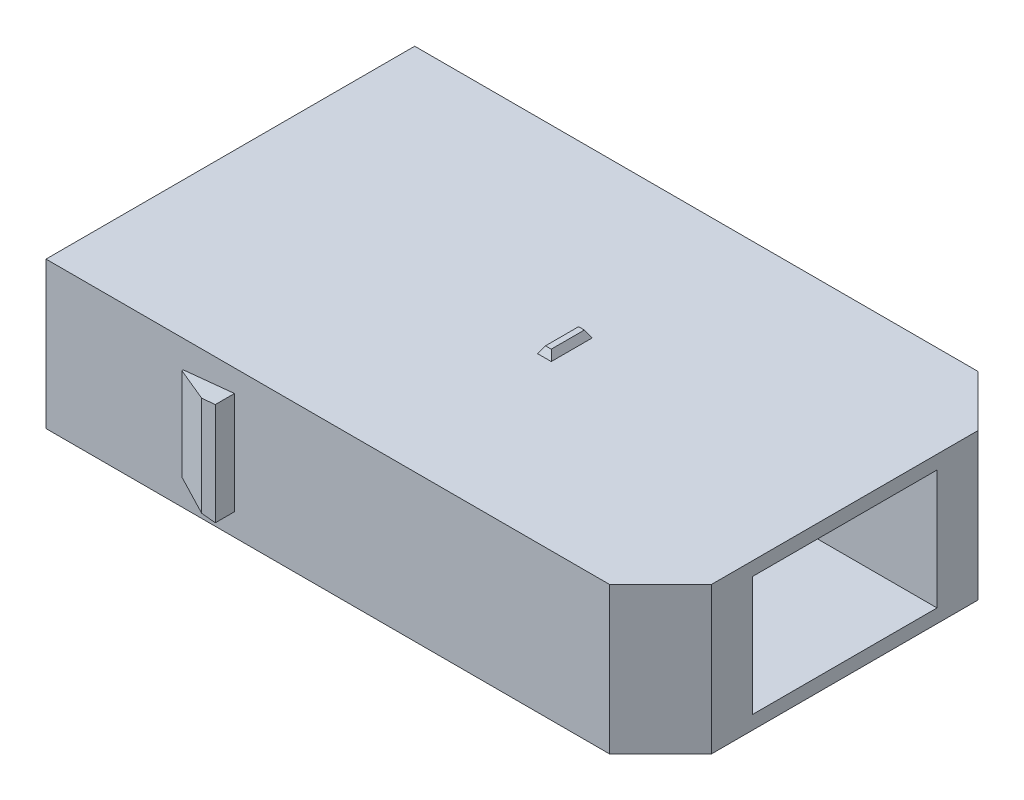
SolidWorks part; units mm, degrees
material "Perspex (TM) GS Acrylic Cast Sheet"
ref_plane "Front Plane" through (0, 0, 0) normal (0, 0, 1) x (1, 0, 0)
ref_plane "Top Plane" through (0, 0, 0) normal (0, 1, 0) x (1, 0, 0)
ref_plane "Right Plane" through (0, 0, 0) normal (1, 0, 0) x (0, 0, -1)
sketch "Sketch1" plane through (0, 0, 0) normal (0, 1, 0) x (1, 0, 0)
  line L1 (0, 0) -> (-22.86, 0)
  line L2 (0, 0) -> (0, 13.716)
  line L3 (0, 13.716) -> (-22.86, 13.716)
  line L4 (-22.86, 0) -> (-22.86, 13.716)
  dimension "D1" = 13.716
  dimension "D2" = 22.86
extrude "Boss-Extrude1" add sketch "Sketch1" along normal blind 5.461
chamfer "Chamfer1" distance 1.905 angle 45 2 edges at (0, 2.7305, -13.716) (0, 2.7305, 0)
sketch "Sketch2" plane through (0, 0, 0) normal (1, 0, 0) x (0, 0, -1)
  line L0 (11.811, 2.7305) -> (10.287, 2.7305) construction
  line L1 (3.429, 4.953) -> (10.287, 4.953)
  line L2 (3.429, 4.953) -> (3.429, 0.508)
  line L3 (3.429, 0.508) -> (10.287, 0.508)
  line L4 (10.287, 4.953) -> (10.287, 0.508)
  line L5 (11.811, 0) -> (11.811, 5.461) construction
  line L6 (1.905, 2.7305) -> (3.429, 2.7305) construction
  line L7 (1.905, 5.461) -> (1.905, 0) construction
  line L8 (6.858, 0) -> (6.858, 0.508) construction
  line L9 (1.905, 0) -> (11.811, 0) construction
  line L10 (6.858, 5.461) -> (6.858, 4.953) construction
  line L11 (1.905, 5.461) -> (11.811, 5.461) construction
  dimension "D1" = 0.508
  dimension "D2" = 1.524
extrude "Cut-Extrude1" cut sketch "Sketch2" against normal blind 5.715
shell "Shell3" thickness 0.508 removed face at (-22.86, 2.7305, -6.858)
sketch "Sketch3" plane through (-5.715, 0, 0) normal (1, 0, 0) x (0, 0, -1)
  line L0 (10.287, 2.7305) -> (3.429, 2.7305) construction
  line L1 (10.287, 0.508) -> (10.287, 4.953) construction
  line L2 (3.429, 4.953) -> (3.429, 0.508) construction
  circle A0 centre (6.858, 2.7305) radius 1.27
  dimension "D1" = 2.54
extrude "Cut-Extrude2" cut sketch "Sketch3" against normal through all
sketch "Sketch4" plane through (0, 5.461, 0) normal (0, 1, 0) x (1, 0, 0)
  line L0 (0, 3.429) -> (0, 10.287) construction
  line L1 (-10.16, 6.096) -> (-10.668, 6.096)
  line L2 (-10.16, 6.096) -> (-10.16, 7.62)
  line L3 (-10.16, 7.62) -> (-10.668, 7.62)
  line L4 (-10.668, 6.096) -> (-10.668, 7.62)
  line L5 (0, 6.858) -> (-10.668, 6.858) construction
  line L6 (0, 1.905) -> (0, 11.811) construction
  dimension "D1" = 10.16
  dimension "D2" = 0.508
  dimension "D3" = 1.524
extrude "Boss-Extrude2" add sketch "Sketch4" along normal blind 0.254 draft 30
sketch "Sketch5" plane through (0, 0, 0) normal (0, -1, 0) x (1, 0, 0)
  line L0 (-10.668, -6.096) -> (-10.16, -6.096) construction
  line L1 (-10.668, -7.62) -> (-10.668, -6.096) construction
  line L2 (-10.16, -6.096) -> (-10.16, -7.62) construction
  line L3 (-10.16, -7.62) -> (-10.668, -7.62) construction
  line L4 (-10.668, -6.096) -> (-10.16, -6.096)
  line L5 (-10.668, -7.62) -> (-10.668, -6.096)
  line L6 (-10.16, -6.096) -> (-10.16, -7.62)
  line L7 (-10.16, -7.62) -> (-10.668, -7.62)
extrude "Boss-Extrude3" add sketch "Sketch5" along normal blind 0.254 draft 30
sketch "Sketch6" plane through (0, 0, 0) normal (0, 0, 1) x (1, 0, 0)
  line L0 (-15.8496, 0.8255) -> (-15.8496, 4.6355)
  line L1 (-15.8496, 4.6355) -> (-17.7546, 4.445)
  line L2 (-17.7546, 4.445) -> (-17.7546, 1.016)
  line L3 (-17.7546, 1.016) -> (-15.8496, 0.8255)
  line L4 (-1.905, 0) -> (-1.905, 5.461) construction
  line L5 (-1.905, 2.7305) -> (-15.8496, 2.7305) construction
  line L7 (-15.8496, 2.7305) -> (-17.7546, 2.7305) construction
  dimension "D2" = 1.905
  dimension "D3" = 3.81
  dimension "D4" = 3.429
  dimension "D5" = 13.9446
extrude "Boss-Extrude4" add sketch "Sketch6" along normal blind 0.7112
sketch "Sketch7" plane through (-0.0752, -0.7519, 0) normal (-0.0995, -0.995, 0) x (-0.995, 0.0995, 0)
  line L0 (17.7676, -0.0508) -> (16.3611, -0.7112)
  line L1 (17.7676, -0.7112) -> (17.7676, 0) construction
  line L2 (16.3611, -0.7112) -> (17.7676, -0.7112)
  line L3 (17.7676, -0.7112) -> (17.7676, -0.0508)
  line L4 (17.7676, -0.7112) -> (15.8531, -0.7112) construction
  line L5 (15.8531, -0.7112) -> (15.8531, 0) construction
  dimension "D1" = 0.0508
  dimension "D2" = 0.508
extrude "Cut-Extrude3" cut sketch "Sketch7" along direction (0, 1, 0) on the side against the normal through all
sketch "Sketch9" plane through (0, 0, -13.716) normal (0, 0, -1) x (-1, 0, 0)
  line L0 (17.7546, 1.016) -> (15.8496, 0.8255) construction
  line L1 (17.7546, 4.445) -> (17.7546, 1.016) construction
  line L2 (15.8496, 4.6355) -> (17.7546, 4.445) construction
  line L3 (15.8496, 0.8255) -> (15.8496, 4.6355) construction
  line L4 (17.7546, 1.016) -> (15.8496, 0.8255)
  line L5 (17.7546, 4.445) -> (17.7546, 1.016)
  line L6 (15.8496, 4.6355) -> (17.7546, 4.445)
  line L7 (15.8496, 0.8255) -> (15.8496, 4.6355)
extrude "Boss-Extrude6" add sketch "Sketch9" along normal blind 0.7112
sketch "Sketch10" plane through (-0.0752, -0.7519, 0) normal (-0.0995, -0.995, 0) x (0.995, -0.0995, 0)
  line L0 (-16.3611, -14.4272) -> (-17.7676, -13.843)
  line L1 (-17.7676, -14.4272) -> (-17.7676, -13.716) construction
  line L2 (-17.7676, -13.843) -> (-17.7676, -14.4272)
  line L3 (-17.7676, -14.4272) -> (-16.3611, -14.4272)
  line L4 (-15.8531, -14.4272) -> (-17.7676, -14.4272) construction
  dimension "D1" = 0.127
  dimension "D2" = 0.508
extrude "Cut-Extrude4" cut sketch "Sketch10" along direction (0, 1, 0) on the side against the normal through all
sketch "Sketch11" plane through (0, 0, -2.921) normal (0, 0, 1) x (1, 0, 0)
  line L0 (-0.7001, 0.6574) -> (-6.223, 4.953) construction
  circle A0 centre (-3.4615, 2.8052) radius 0.635
  dimension "D1" = 1.27
extrude "Cut-Extrude5" cut sketch "Sketch11" against normal up to surface (10.287 mm away) up to face at (-12.4877, 2.7305, -13.208)
sketch "Sketch12" plane through (-5.715, 0, 0) normal (1, 0, 0) x (0, 0, -1)
  line L0 (5.969, 3.6375) -> (5.969, 4.2952)
  line L1 (5.969, 4.2952) -> (7.747, 4.2952)
  line L2 (7.747, 4.2952) -> (7.747, 3.6375)
  line L3 (5.969, 1.8235) -> (5.969, 1.1658)
  line L4 (5.969, 1.1658) -> (7.747, 1.1658)
  line L5 (7.747, 1.1658) -> (7.747, 1.8235)
  line L8 (3.429, 0.508) -> (10.287, 0.508) construction
  arc A0 (5.969, 1.8235) -> (7.747, 1.8235) centre (6.858, 2.7305) ccw
  arc A1 (7.747, 3.6375) -> (5.969, 3.6375) centre (6.858, 2.7305) ccw
  circle A2 centre (6.858, 2.7305) radius 1.27 construction
extrude "Cut-Extrude6" cut sketch "Sketch12" against normal through all
